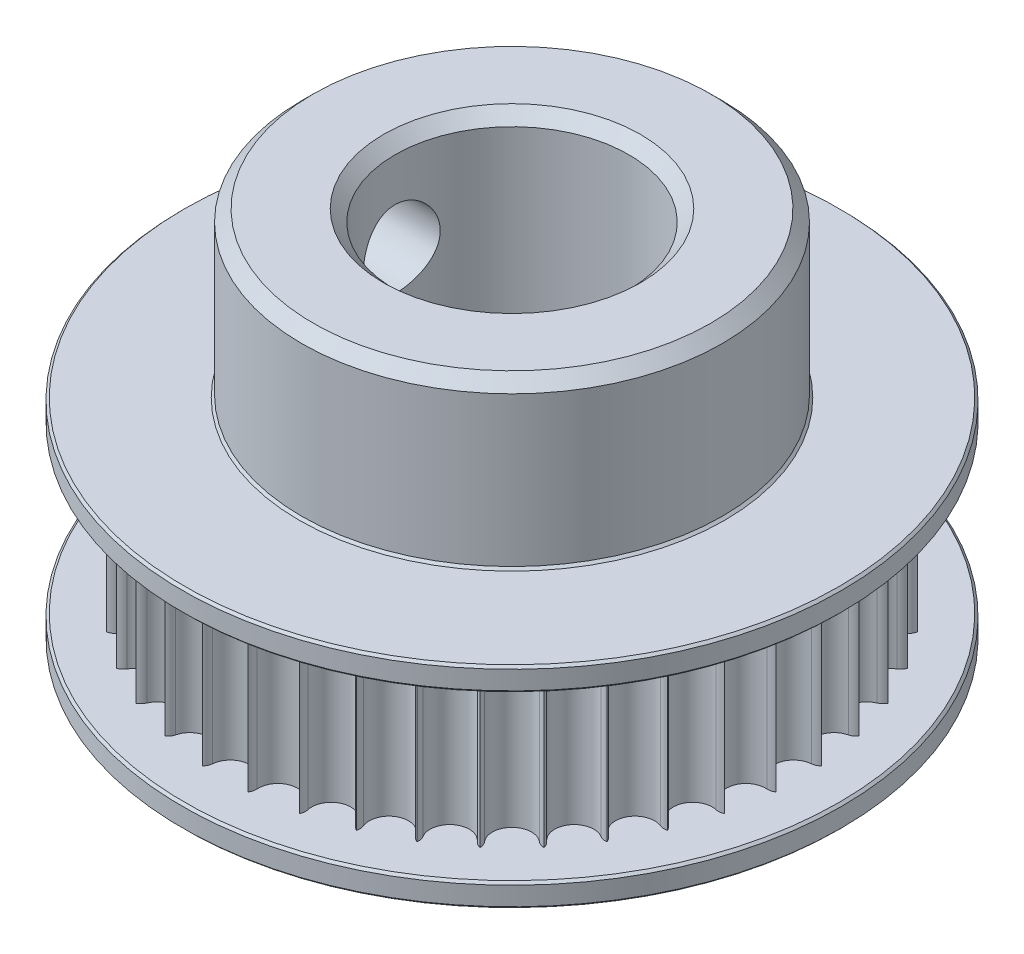
SolidWorks part; units mm, degrees
ref_plane "Front plan" through (0, 0, 0) normal (0, 0, 1) x (1, 0, 0)
ref_plane "Top plan" through (0, 0, 0) normal (0, 1, 0) x (1, 0, 0)
ref_plane "Right plan" through (0, 0, 0) normal (1, 0, 0) x (0, 0, -1)
sketch "Skica2" plane through (0, 0, 0) normal (0, 0, 1) x (1, 0, 0)
  line L0 (9, 8.5) -> (5, 8.5)
  line L1 (5, 8.5) -> (5, -8.5)
  line L2 (5, -8.5) -> (6.11, -8.5)
  line L3 (0, -8.5) -> (0, 8.5) construction
  line L4 (0, 8.5) -> (5, 8.5)
  line L5 (0, -8.5) -> (5, -8.5)
  line L6 (6.11, -8.5) -> (6.11, -7.5)
  line L7 (14.1, 0.5) -> (12.5, 0.5)
  line L8 (12.5, 0.5) -> (12.5, -6.5)
  line L9 (14.1, 0.5) -> (14.1, 1.5)
  line L12 (14.1, -7.5) -> (6.11, -7.5)
  line L13 (14.1, 1.5) -> (9, 1.5)
  line L14 (14.1, -7.5) -> (14.1, -6.5)
  line L15 (12.5, -6.5) -> (14.1, -6.5)
  line L16 (9, 1.5) -> (9, 8.5)
  point P6 (10.105, -7.5)
  point P7 (0, 0)
  dimension "D2" = 1
  dimension "D6" = 28.2
  dimension "D3" = 25
  dimension "D1" = 10
  dimension "D8" = 17
  dimension "D4" = 1
  dimension "D7" = 18
  dimension "D9" = 7
revolve "Revolute" add sketch "Skica2" angle 360 about L3 region at (8.3694, -0.8113, 0)
sketch "Sketch2" plane through (0, 0.5, 0) normal (0, -1, 0) x (1, 0, 0)
  line L0 (0, 0) -> (0, 12.0464) construction
  line L1 (0, 0) -> (4.215, 11.7679) construction
  line L3 (0, 0) -> (-2.1557, 12.3127) construction
  circle A1 centre (0, 0) radius 11.2105 construction
  circle A2 centre (0, 0) radius 12 construction
  arc A3 (-0.8326, 11.9711) -> (0.8326, 11.9711) centre (0, 12.0464) ccw
  arc A7 (-1.386, 12.4229) -> (-2.1557, 12.3127) centre (0, 0) ccw
  arc A8 (0, 13.9436) -> (2.1557, 12.3127) centre (0.592, 12.486) cw
  circle A9 centre (0, 0) radius 12.5 construction
  arc A10 (1.386, 12.4229) -> (2.1557, 12.3127) centre (0, 0) cw
  arc A11 (1.386, 12.4229) -> (0.8326, 11.9711) centre (1.3305, 11.926) ccw
  arc A12 (0, 13.9436) -> (-2.1557, 12.3127) centre (-0.592, 12.486) ccw
  arc A13 (-1.386, 12.4229) -> (-0.8326, 11.9711) centre (-1.3305, 11.926) cw
  point P0 (0.8326, 11.926)
  dimension "D2" = 1
  dimension "D4" = 0.836
  dimension "D6" = 25
  dimension "D3" = 1.5733
  dimension "D1" = 0.5
extrude "Cut-Extrude3" cut sketch "Sketch2" along normal up to surface (7 mm away) up to face at (14.1, -6.5, 0)
pattern_circular "CirPattern1" count 40 over 360 about axis through (0, -8.5, 0) along (0, -1, 0) of "Cut-Extrude3"
sketch "Sketch3" plane through (0, 0, 0) normal (1, 0, 0) x (0, 0, -1)
  line L0 (0, 8.5) -> (0, 0.5) construction
  line L1 (5, 8.5) -> (-5, 8.5) construction
  circle A0 centre (0, 4.5) radius 1.65
  dimension "D1" = 3.3
extrude "Cut-Extrude2" cut sketch "Sketch3" against normal up to next
chamfer "Chamfer1" distance 1 angle 45 1 edges at (6.11, -7.5, 0)
chamfer "Chamfer2" distance 0.5 angle 45 2 edges at (9, 8.5, 0) (5, 8.5, 0)
chamfer "Chamfer3" distance 0.1 angle 45 5 edges at (14.1, -7.5, 0) (14.1, -6.5, 0) (14.1, 0.5, 0) (14.1, 1.5, 0) (9, 1.5, 0)
equation "\"`\"=2"
equation "\"D6@Sketch2\"= \"D3@Skica2\""
